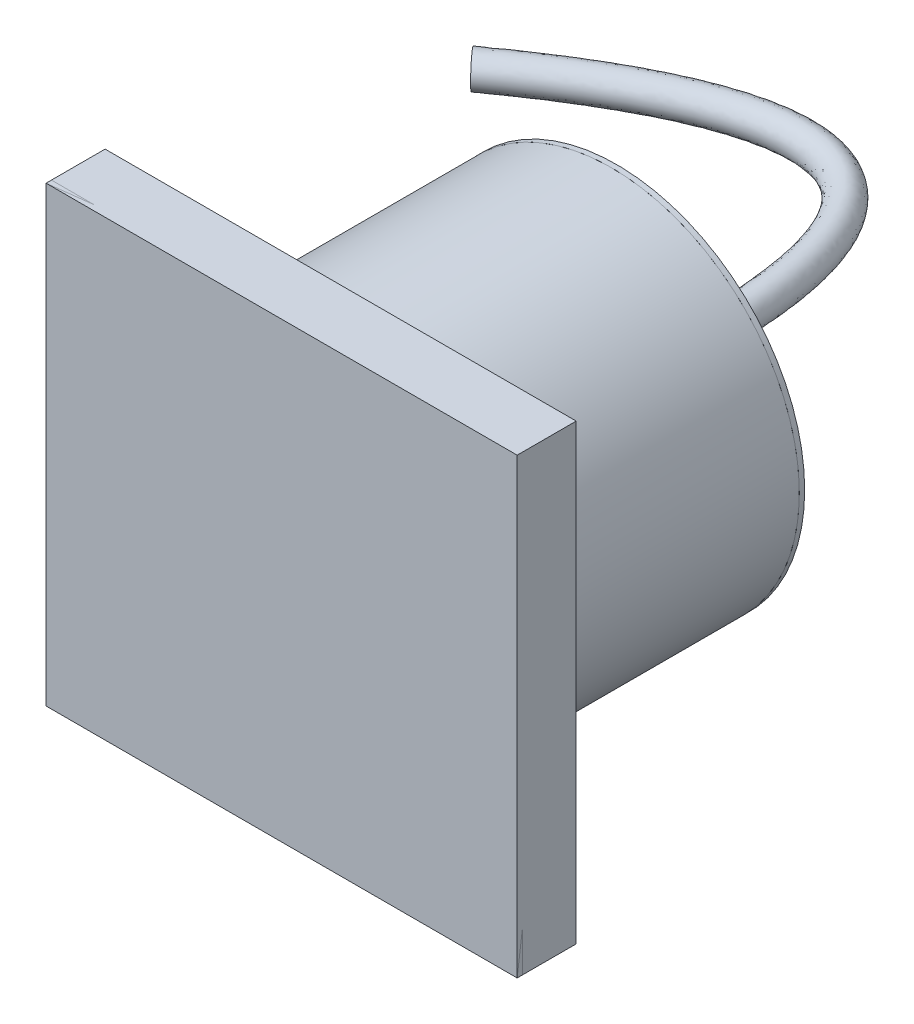
SolidWorks part; units mm, degrees
ref_plane "Front Plane" through (0, 0, 0) normal (0, 0, 1) x (1, 0, 0)
ref_plane "Top Plane" through (0, 0, 0) normal (0, 1, 0) x (1, 0, 0)
ref_plane "Right Plane" through (0, 0, 0) normal (1, 0, 0) x (0, 0, -1)
sketch "Sketch1" plane through (0, 0, 0) normal (0, 0, 1) x (1, 0, 0)
  circle A0 centre (0, 0) radius 25
  circle A1 centre (0, 0) radius 35
  dimension "D2" = 50
  dimension "D1" = 10
extrude "Boss-Extrude1" add sketch "Sketch1" along normal blind 61
surface "Surface-Extrude1" sketch "Sketch1<2>" parameters "D1"=1
sketch "Sketch1<2>" plane through (0, 0, 0) normal (0, 0, 1) x (1, 0, 0) same geometry as "Sketch1"
sketch "Sketch2" plane through (0, 0, -1) normal (0, 0, -1) x (-1, 0, 0)
  circle A0 centre (0, 0) radius 3.0395
sketch "Sketch3" plane through (0, 0, 0) normal (0, 1, 0) x (1, 0, 0)
  line L0 (3.0395, 1) -> (-3.0395, 1) construction
  spline S0 degree 2 poles (0, 1) (7.9926, 89.8431) (-63.892, 37.9464) knots 0 0 0 1 1 1
sweep "Sweep1" add profiles "Sketch2" path "Sketch3"
sketch "Sketch4" plane through (0, 0, 0) normal (0, 0, 1) x (1, 0, 0)
  line L1 (-44.3402, 40.8339) -> (43.4301, 40.8339)
  line L2 (-44.3402, 40.8339) -> (-44.3402, -43.5262)
  line L3 (-44.3402, -43.5262) -> (43.4301, -43.5262)
  line L4 (43.4301, 40.8339) -> (43.4301, -43.5262)
  circle A0 centre (0, 0) radius 35
extrude "Boss-Extrude2" add sketch "Sketch4" along normal blind 10 from offset 50
surface "Surface-Extrude2" sketch "Sketch4<2>" parameters "D1"=1
sketch "Sketch4<2>" plane through (0, 0, 0) normal (0, 0, 1) x (1, 0, 0) same geometry as "Sketch4"
sketch "Sketch6" plane through (0, 0, 0) normal (0, 0, 1) x (1, 0, 0)
  line L1 (-44.3402, 40.8339) -> (43.4301, 40.8339)
  line L2 (-44.3402, 40.8339) -> (-44.3402, -43.5262)
  line L3 (-44.3402, -43.5262) -> (43.4301, -43.5262)
  line L4 (43.4301, 40.8339) -> (43.4301, -43.5262)
extrude "Boss-Extrude3" add sketch "Sketch6" along normal blind 1 from offset 60
